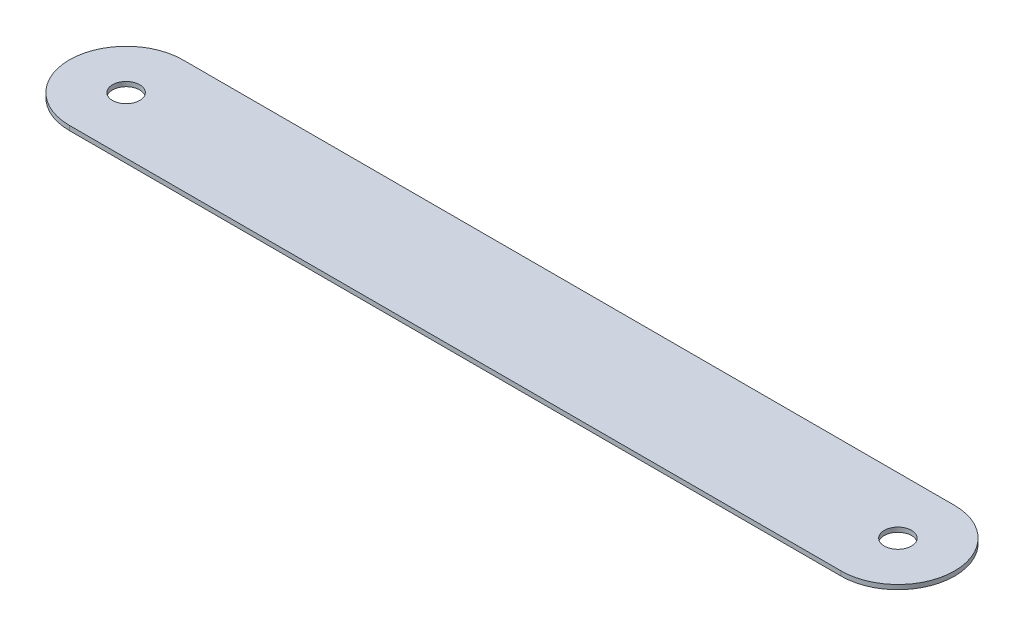
SolidWorks part; units mm, degrees
ref_plane "前基準面" through (0, 0, 0) normal (0, 0, 1) x (1, 0, 0)
ref_plane "上基準面" through (0, 0, 0) normal (0, 1, 0) x (1, 0, 0)
ref_plane "右基準面" through (0, 0, 0) normal (1, 0, 0) x (0, 0, -1)
sketch "草圖1" plane through (0, 0, 0) normal (0, 1, 0) x (1, 0, 0)
  line L0 (-42.5, 0) -> (42.5, 0) construction
  line L1 (-42.5, 6.25) -> (42.5, 6.25)
  line L2 (-42.5, -6.25) -> (42.5, -6.25)
  arc A0 (-42.5, 6.25) -> (-42.5, -6.25) centre (-42.5, 0) ccw
  arc A1 (42.5, -6.25) -> (42.5, 6.25) centre (42.5, 0) ccw
  circle A2 centre (-42.5, 0) radius 1.5
  circle A3 centre (42.5, 0) radius 1.5
  point P2 (0, 0)
  dimension "D1" = 85
  dimension "D2" = 12.5
extrude "填料-伸長1" add sketch "草圖1" along normal blind 0.5
